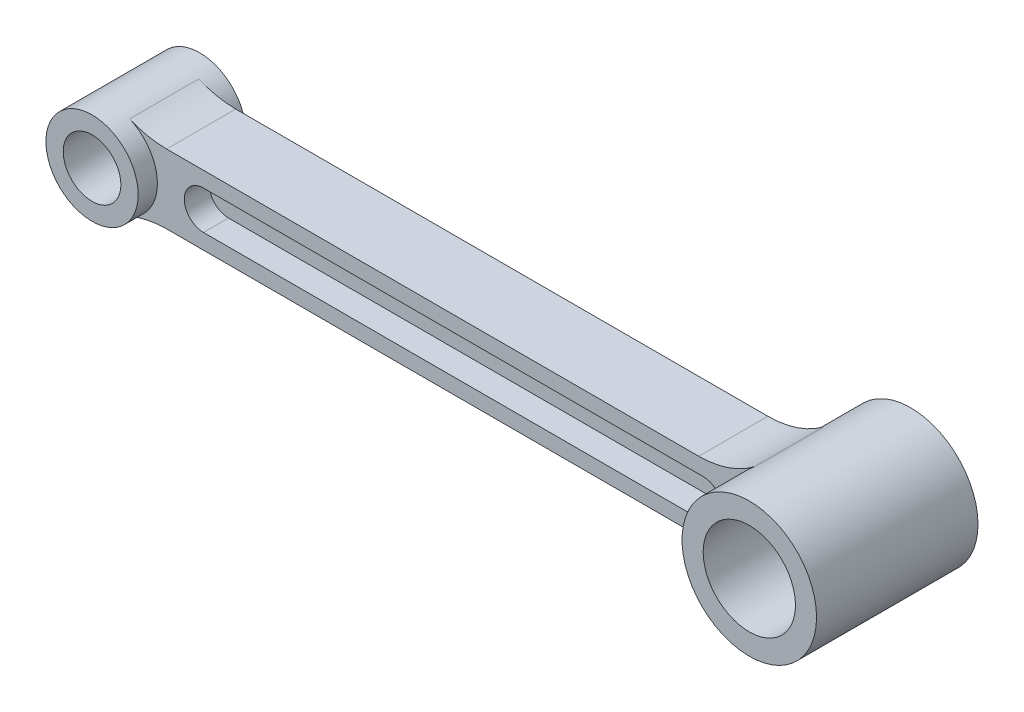
SolidWorks part; units mm, degrees
ref_plane "Front Plane" through (0, 0, 0) normal (0, 0, 1) x (1, 0, 0)
ref_plane "Top Plane" through (0, 0, 0) normal (0, 1, 0) x (1, 0, 0)
ref_plane "Right Plane" through (0, 0, 0) normal (1, 0, 0) x (0, 0, -1)
sketch "Sketch1" plane through (0, 0, 0) normal (0, 0, 1) x (1, 0, 0)
  line L0 (65, 0) -> (-65, 0) construction
  line L1 (65, -5) -> (-65, -5)
  line L2 (65, 5) -> (-65, 5)
  line L3 (0, 36.8421) -> (0, -35.4995) construction
  line L4 (-172.3721, 0) -> (153.3979, 0) construction
  line L5 (-89, 55.4834) -> (-89, -51.5694) construction
  line L6 (89, 55.4834) -> (89, -51.5694) construction
  line L7 (-74.6125, 9) -> (63.8355, 9)
  line L8 (-74.6125, -9) -> (63.8355, -9)
  arc A0 (65, -5) -> (65, 5) centre (65, 0) ccw
  arc A1 (-65, 5) -> (-65, -5) centre (-65, 0) ccw
  circle A2 centre (-89, 0) radius 7.5
  circle A3 centre (-89, 0) radius 12
  circle A4 centre (89, 0) radius 17.5
  circle A5 centre (89, 0) radius 12
  arc A6 (-84.2042, 11) -> (-74.6125, 9) centre (-74.6125, 33) ccw
  arc A7 (63.8355, 9) -> (78.3885, 13.9157) centre (63.8355, 33) ccw
  arc A8 (63.8355, -9) -> (78.3885, -13.9157) centre (63.8355, -33) cw
  arc A9 (-84.2042, -11) -> (-74.6125, -9) centre (-74.6125, -33) cw
  point P3 (0, 0)
  dimension "D5" = 35
  dimension "D6" = 24
  dimension "D7" = 15
  dimension "D8" = 24
  dimension "D9" = 9
  dimension "D10" = 24
  dimension "D11" = 24
  dimension "D1" = 10
  dimension "D2" = 130
  dimension "D3" = 178
  dimension "D4" = 89
extrude "Boss-Extrude1" add sketch "Sketch1" along normal mid plane 28 contours A3 A2 region at (-79.2453, 6.3886, 0)
extrude "Boss-Extrude2" add sketch "Sketch1<3>" along normal mid plane 42 separate body contours A4 A5 region at (96.5441, 15.24, 0)
sketch "Sketch1<3>" plane through (0, 0, 0) normal (0, 0, 1) x (1, 0, 0) same geometry as "Sketch1"
extrude "Boss-Extrude3" add sketch "Sketch1<4>" along normal mid plane 18 contours A3 A9 L8 A8 A4 A7 L7 A6 A1 L2 A0 L1 region at (-5.3885, 7.3504, 0)
sketch "Sketch1<4>" plane through (0, 0, 0) normal (0, 0, 1) x (1, 0, 0) same geometry as "Sketch1"
extrude "Boss-Extrude4" add sketch "Sketch1<5>" along normal mid plane 5 contours L2 A1 L1 A0 region at (0, 0, 0)
sketch "Sketch1<5>" plane through (0, 0, 0) normal (0, 0, 1) x (1, 0, 0) same geometry as "Sketch1"
